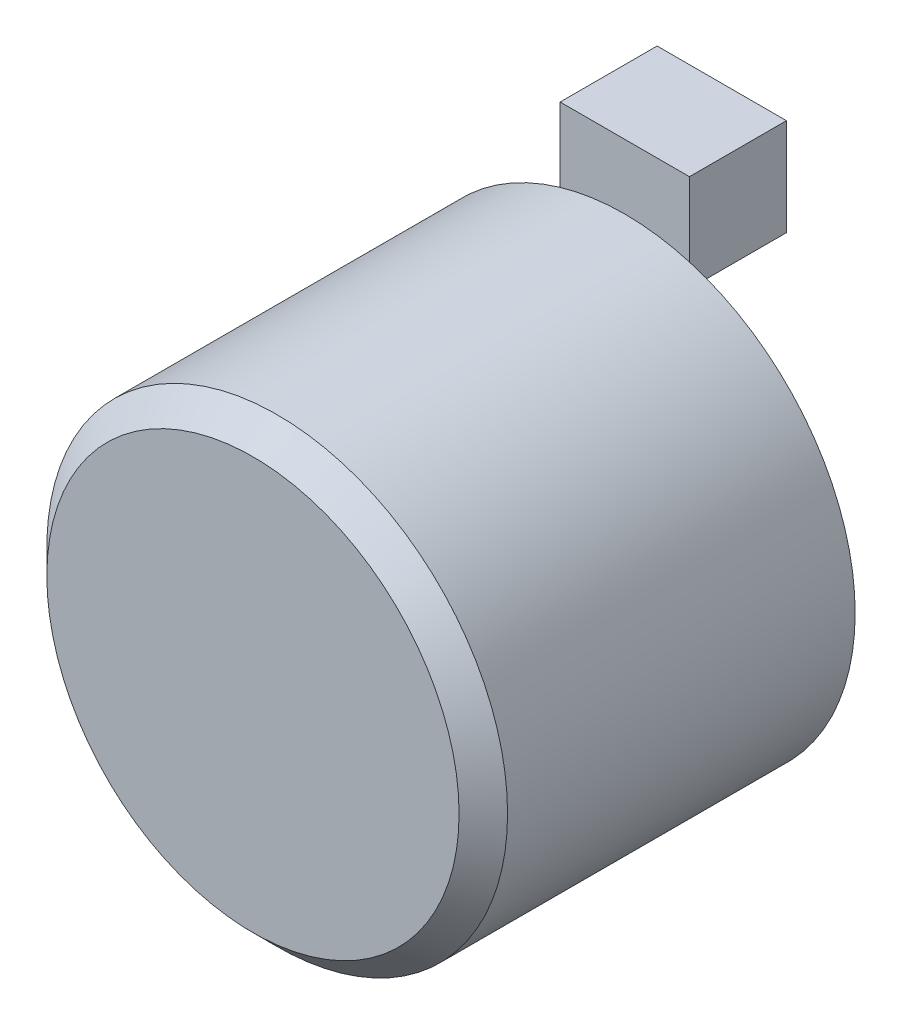
SolidWorks part; units mm, degrees
ref_plane "Front Plane" through (0, 0, 0) normal (0, 0, 1) x (1, 0, 0)
ref_plane "Top Plane" through (0, 0, 0) normal (0, 1, 0) x (1, 0, 0)
ref_plane "Right Plane" through (0, 0, 0) normal (1, 0, 0) x (0, 0, -1)
sketch "SK_Body" plane through (0, 0, 0) normal (0, 1, 0) x (1, 0, 0)
  line L0 (0, -10) -> (0, 56) construction
  line L1 (0, 0) -> (25.5, 0)
  line L2 (25.5, 0) -> (28.5, 3)
  line L3 (28.5, 3) -> (28.5, 46)
  line L4 (28.5, 46) -> (25.5, 46)
  line L5 (25.5, 46) -> (0, 46)
  line L6 (0, 46) -> (0, 0)
  dimension "P1" = 10
  dimension "P2" = 56
  dimension "R_front" = 25.5
  dimension "P4" = 28.5
  dimension "P5" = 3
  dimension "R_body" = 28.5
  dimension "L_body" = 46
  dimension "P8" = 25.5
  dimension "P9" = 46
  dimension "P10" = 46
revolve "Housing_Body" add sketch "SK_Body" angle 360 about L0
ref_plane "PL_Rear" through (0, 0, -46) normal (0, 0, 1) x (1, 0, 0)
sketch "SK_RearHole" plane through (0, 0, -46) normal (0, 0, 1) x (1, 0, 0)
  circle A0 centre (23, 0) radius 1.25
  dimension "D_rh" = 2.5
  dimension "R_rh" = 23
extrude "Rear_Tapped_Hole" cut sketch "SK_RearHole" along normal blind 8
ref_axis "AX_Joint" through (0, 0, -60.9) along (0, 0, 1)
pattern_circular "Rear_Hole_Pattern" count 4 over 360 about axis through (0, 0, -60.9) along (0, 0, 1) of "Rear_Tapped_Hole"
sketch "SK_Connector" plane through (0, 0, -46) normal (0, 0, 1) x (1, 0, 0)
  line L0 (-8, 24.5) -> (8, 24.5)
  line L1 (8, 24.5) -> (8, 36.5)
  line L2 (8, 36.5) -> (-8, 36.5)
  line L3 (-8, 36.5) -> (-8, 24.5)
  dimension "P1" = 8
  dimension "P2" = 24.5
  dimension "P3" = 8
  dimension "P4" = 24.5
  dimension "P5" = 8
  dimension "P6" = 36.5
  dimension "P7" = 8
  dimension "P8" = 36.5
extrude "Connector_Zone" add sketch "SK_Connector" against normal blind 12
equation "\"D_act\" = 57"
equation "\"L_housing\" = 46"
equation "\"PCD_rear\" = 46"
equation "\"D_rear_hole\" = 2.5"
equation "\"D_bearing_boss\" = 36"
equation "\"R_front@SK_Body\" = \"D_act\"/2-3.0"
equation "\"R_body@SK_Body\" = \"D_act\"/2"
equation "\"L_body@SK_Body\" = \"L_housing\""
equation "\"D_rh@SK_RearHole\" = \"D_rear_hole\""
equation "\"R_rh@SK_RearHole\" = \"PCD_rear\"/2"
